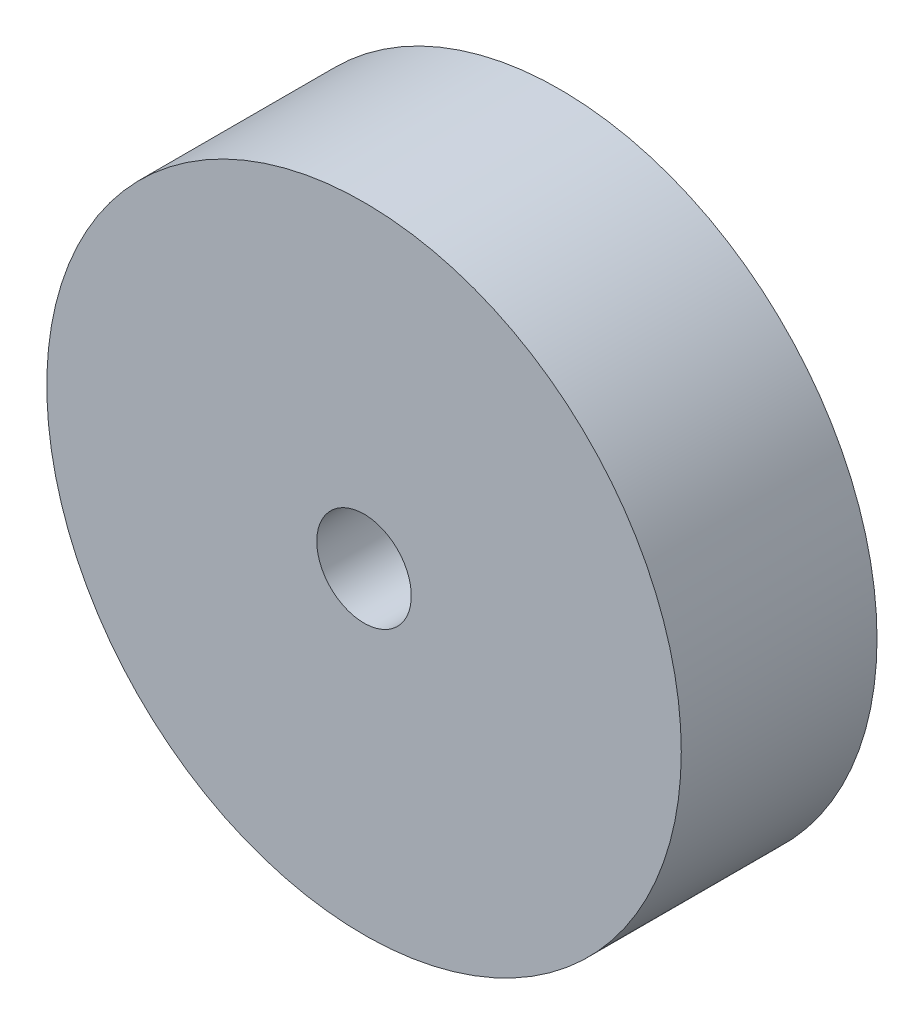
SolidWorks part; units mm, degrees
ref_plane "Front Plane" through (0, 0, 0) normal (0, 0, 1) x (1, 0, 0)
ref_plane "Top Plane" through (0, 0, 0) normal (0, 1, 0) x (1, 0, 0)
ref_plane "Right Plane" through (0, 0, 0) normal (1, 0, 0) x (0, 0, -1)
sketch "Sketch1" plane through (0, 0, 0) normal (0, 0, 1) x (1, 0, 0)
  circle A0 centre (-29.0823, -1.7038) radius 9.4
  dimension "D1" = 18.8
extrude "Boss-Extrude1" add sketch "Sketch1" along normal blind 5.8
sketch "Sketch2" plane through (0, 0, 0) normal (0, 0, -1) x (-1, 0, 0)
  circle A0 centre (29.0823, -1.7038) radius 7.95
  dimension "D1" = 15.9
extrude "Cut-Extrude1" cut sketch "Sketch2" against normal blind 3.2
sketch "Sketch3" plane through (0, 0, 3.2) normal (0, 0, -1) x (-1, 0, 0)
  circle A0 centre (29.0823, -1.7038) radius 1
  dimension "D1" = 2
extrude "Boss-Extrude2" add sketch "Sketch3" along normal blind 1.5875
sketch "Sketch4" plane through (0, 0, 1.6125) normal (0, 0, -1) x (-1, 0, 0)
  circle A0 centre (29.0823, -1.7038) radius 3.7
  dimension "D1" = 7.4
extrude "Boss-Extrude3" add sketch "Sketch4" against normal blind 3
sketch "Sketch5" plane through (0, 0, 1.6125) normal (0, 0, -1) x (-1, 0, 0)
  circle A0 centre (29.0823, -1.7038) radius 1.4
  dimension "D1" = 2.8
extrude "Cut-Extrude2" cut sketch "Sketch5" against normal through all
chamfer "Chamfer2" distance 1.7 angle 41 1 edges at (-32.7823, -1.7038, 1.6125) first distance on face at (-32.7823, -1.7038, 3.2)
